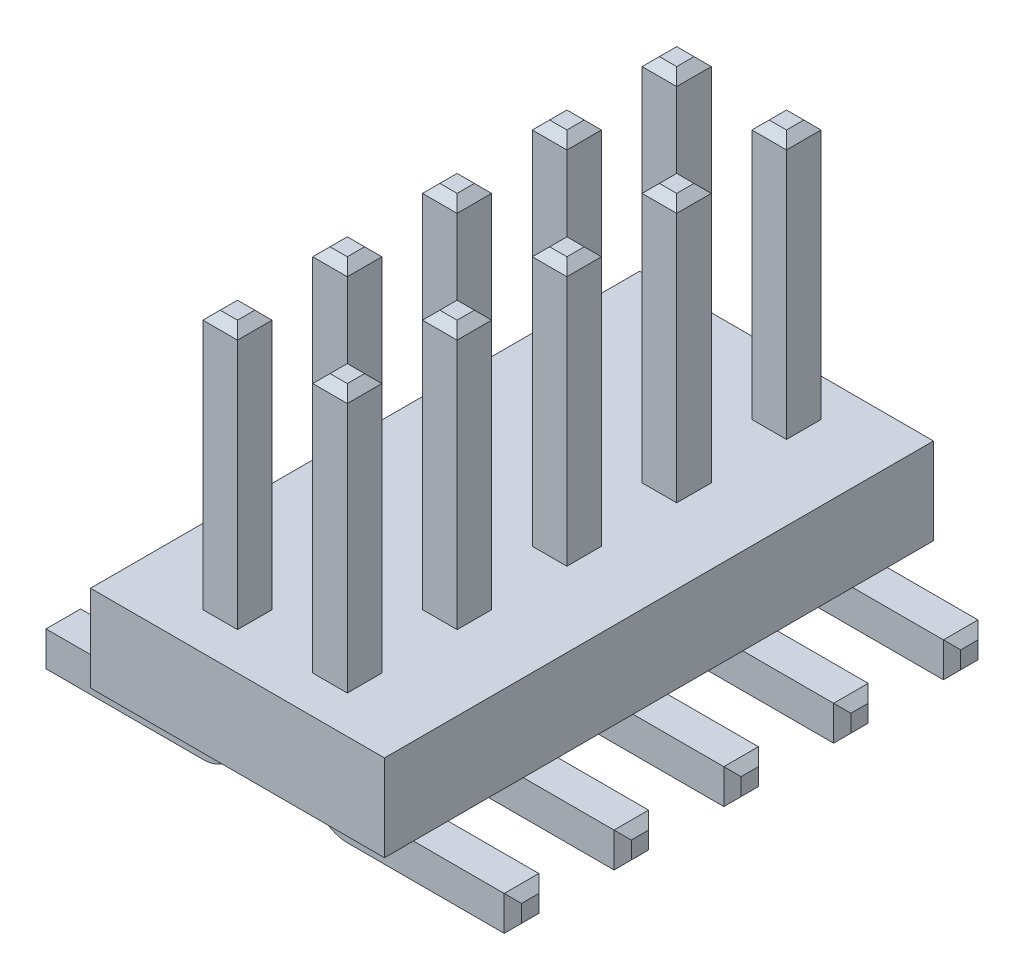
SolidWorks part; units mm, degrees
ref_plane "Vorne" through (0, 0, 0) normal (0, 0, 1) x (1, 0, 0)
ref_plane "Oben" through (0, 0, 0) normal (0, 1, 0) x (1, 0, 0)
ref_plane "Rechts" through (0, 0, 0) normal (1, 0, 0) x (0, 0, -1)
sketch "Skizze1" plane through (0, 0, 0) normal (0, 0, 1) x (1, 0, 0)
  line L1 (0, 0) -> (3.4, 0)
  line L2 (0, 0) -> (0, 1)
  line L3 (0, 1) -> (3.4, 1)
  line L4 (3.4, 0) -> (3.4, 1)
  dimension "D1" = 3.4
  dimension "D2" = 1
extrude "Aufsatz-Linear austragen1" add sketch "Skizze1" along normal blind 1.27
sketch "Skizze3" plane through (0, 0, 0) normal (0, -1, 0) x (1, 0, 0)
  line L28 (0.865, 0.435) -> (1.265, 0.435)
  line L29 (0.865, 0.435) -> (0.865, 0.835)
  line L30 (0.865, 0.835) -> (1.265, 0.835)
  line L31 (1.265, 0.435) -> (1.265, 0.835)
  line L32 (0.865, 0.435) -> (1.265, 0.835) construction
  line L33 (0.865, 0.835) -> (1.265, 0.435) construction
  line L34 (2.135, 0.435) -> (2.535, 0.435)
  line L35 (2.135, 0.435) -> (2.135, 0.835)
  line L36 (2.135, 0.835) -> (2.535, 0.835)
  line L37 (2.535, 0.435) -> (2.535, 0.835)
  line L38 (2.135, 0.435) -> (2.535, 0.835) construction
  line L39 (2.135, 0.835) -> (2.535, 0.435) construction
  line L40 (0.865, 2.975) -> (1.265, 2.975)
  line L41 (0.865, 2.975) -> (0.865, 3.375)
  line L42 (0.865, 3.375) -> (1.265, 3.375)
  line L43 (1.265, 2.975) -> (1.265, 3.375)
  line L44 (2.135, 2.975) -> (2.535, 2.975)
  line L45 (2.135, 2.975) -> (2.135, 3.375)
  line L46 (2.135, 3.375) -> (2.535, 3.375)
  line L47 (2.535, 2.975) -> (2.535, 3.375)
  line L48 (0.865, 2.975) -> (1.265, 3.375) construction
  line L49 (0.865, 3.375) -> (1.265, 2.975) construction
  line L50 (2.135, 2.975) -> (2.535, 3.375) construction
  line L51 (2.135, 3.375) -> (2.535, 2.975) construction
  line L52 (0.865, 1.705) -> (1.265, 1.705)
  line L53 (0.865, 1.705) -> (0.865, 2.105)
  line L54 (0.865, 2.105) -> (1.265, 2.105)
  line L55 (1.265, 1.705) -> (1.265, 2.105)
  line L56 (2.135, 1.705) -> (2.535, 1.705)
  line L57 (2.135, 1.705) -> (2.135, 2.105)
  line L58 (2.135, 2.105) -> (2.535, 2.105)
  line L59 (2.535, 1.705) -> (2.535, 2.105)
  line L60 (0.865, 1.705) -> (1.265, 2.105) construction
  line L61 (0.865, 2.105) -> (1.265, 1.705) construction
  line L62 (2.135, 1.705) -> (2.535, 2.105) construction
  line L63 (2.135, 2.105) -> (2.535, 1.705) construction
  point P0 (2.335, 1.905)
  point P1 (2.335, 3.175)
  point P2 (1.065, 3.175)
  point P3 (1.065, 1.905)
  point P27 (1.065, 0.635)
  point P32 (2.335, 0.635)
extrude "Aufsatz-Linear austragen3" add sketch "Skizze3" along normal blind 0.5
sketch "Skizze4" plane through (2.535, 0, 0) normal (1, 0, 0) x (0, 0, -1)
  line L10 (-0.435, -0.5) -> (-0.435, 0) construction
  line L11 (-0.835, -0.5) -> (-0.435, -0.5)
  line L12 (-0.835, -0.5) -> (-0.835, -0.1)
  line L13 (-0.835, -0.1) -> (-0.435, -0.1)
  line L14 (-0.435, -0.5) -> (-0.435, -0.1)
  dimension "D1" = 0.4
extrude "Aufsatz-Linear austragen4" add sketch "Skizze4" along normal blind 1.915
sketch "Skizze5" plane through (0.865, 0, 0) normal (-1, 0, 0) x (0, 0, 1)
  line L9 (0.435, -0.5) -> (0.435, 0) construction
  line L10 (0.835, -0.5) -> (0.435, -0.5)
  line L11 (0.835, -0.5) -> (0.835, -0.1)
  line L12 (0.835, -0.1) -> (0.435, -0.1)
  line L13 (0.435, -0.5) -> (0.435, -0.1)
extrude "Aufsatz-Linear austragen5" add sketch "Skizze5" along normal blind 1.915
sketch "Skizze6" plane through (0, 1, 0) normal (0, 1, 0) x (1, 0, 0)
  line L0 (3.4, 0) -> (0, 0) construction
  line L1 (0.865, -0.835) -> (1.265, -0.835)
  line L2 (0.865, -0.835) -> (0.865, -0.435)
  line L3 (0.865, -0.435) -> (1.265, -0.435)
  line L4 (1.265, -0.835) -> (1.265, -0.435)
  line L5 (0.865, -0.835) -> (1.265, -0.435) construction
  line L6 (0.865, -0.435) -> (1.265, -0.835) construction
  line L7 (0, -1.27) -> (0, 0) construction
  line L8 (2.135, -0.835) -> (2.535, -0.835)
  line L9 (2.135, -0.835) -> (2.135, -0.435)
  line L10 (2.135, -0.435) -> (2.535, -0.435)
  line L11 (2.535, -0.835) -> (2.535, -0.435)
  line L12 (2.135, -0.835) -> (2.535, -0.435) construction
  line L13 (2.135, -0.435) -> (2.535, -0.835) construction
  point P0 (1.065, -0.635)
  point P11 (2.335, -0.635)
  dimension "D1" = 0.4
  dimension "D2" = 0.4
  dimension "D3" = 0.635
  dimension "D4" = 1.065
  dimension "D5" = 1
extrude "Aufsatz-Linear austragen6" add sketch "Skizze6" along normal blind 3
chamfer "Fase2" distance 0.1 angle 45 16 edges at (-1.05, -0.1, 0.635) (-1.05, -0.3, 0.835) (-1.05, -0.5, 0.635) (-1.05, -0.3, 0.435) (4.45, -0.3, 0.835) (4.45, -0.1, 0.635) (4.45, -0.3, 0.435) (4.45, -0.5, 0.635) (2.335, 4, 0.835) (2.535, 4, 0.635) (2.335, 4, 0.435) (2.135, 4, 0.635) (1.065, 4, 0.835) (1.265, 4, 0.635) (1.065, 4, 0.435) (0.865, 4, 0.635)
fillet "Verrundung1" radius 0.1 2 edges at (0.865, -0.1, 0.635) (2.535, -0.1, 0.635)
fillet "Verrundung2" radius 0.4 2 edges at (2.135, -0.5, 0.635) (1.265, -0.5, 0.635)
pattern_linear "Lineares Muster1" count 5 spacing 1.27 along (0, 0, 1) of "Aufsatz-Linear austragen1", "Aufsatz-Linear austragen3", "Aufsatz-Linear austragen4", "Aufsatz-Linear austragen5", "Aufsatz-Linear austragen6", "Fase2", "Verrundung1", "Verrundung2"
